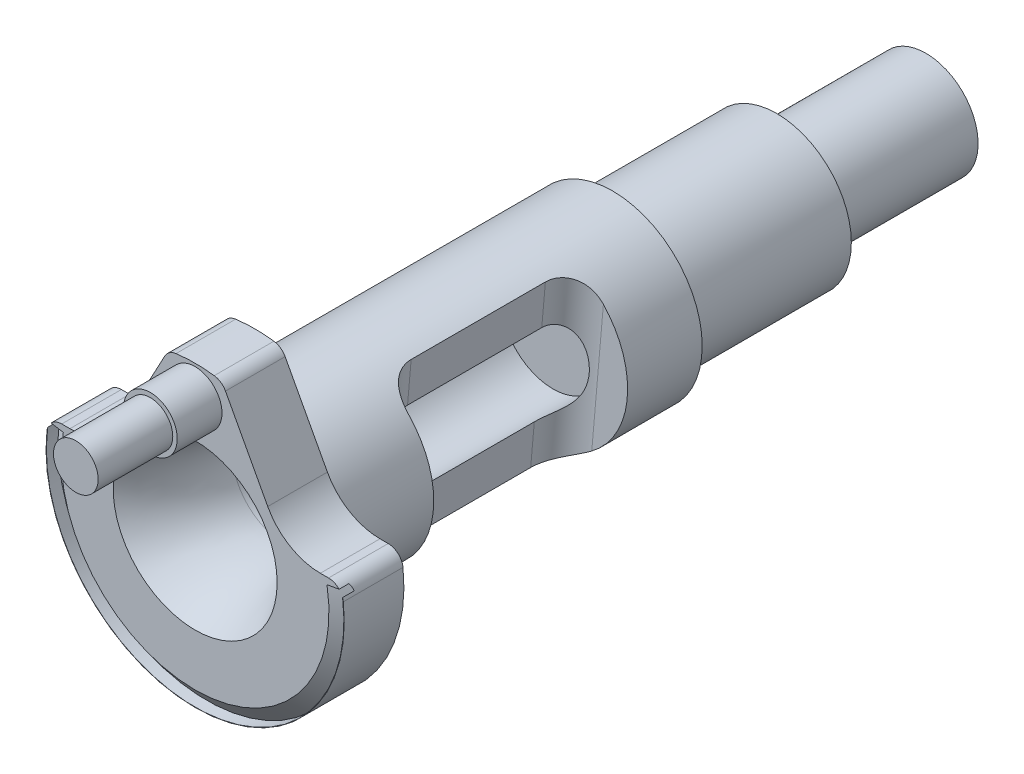
SolidWorks part; units mm, degrees
ref_plane "Front Plane" through (0, 0, 0) normal (0, 0, 1) x (1, 0, 0)
ref_plane "Top Plane" through (0, 0, 0) normal (0, 1, 0) x (1, 0, 0)
ref_plane "Right Plane" through (0, 0, 0) normal (1, 0, 0) x (0, 0, -1)
sketch "Sketch1" plane through (0, 0, 0) normal (0, 0, 1) x (1, 0, 0)
  circle A0 centre (0, 0) radius 5
  dimension "D1" = 10
extrude "Boss-Extrude1" add sketch "Sketch1" along normal blind 35
sketch "Sketch3" plane through (0, 0, 35) normal (0, 0, 1) x (1, 0, 0)
  circle A0 centre (0, 0) radius 5 construction
  circle A1 centre (0, 0) radius 5
  circle A2 centre (0, 0) radius 10
  dimension "D1" = 20
extrude "Boss-Extrude3" add sketch "Sketch3" along normal blind 4 contours A2
sketch "Sketch4" plane through (0, 0, 35) normal (0, 0, -1) x (-1, 0, 0)
  circle A0 centre (0, 0) radius 5 construction
  circle A1 centre (0, 0) radius 5
  circle A2 centre (0, 0) radius 6
  dimension "D1" = 12
extrude "Boss-Extrude4" add sketch "Sketch4" along normal blind 24
sketch "Sketch5" plane through (0, 0, 39) normal (0, 0, 1) x (1, 0, 0)
  line L0 (0, 0) -> (0, 50000) construction
  line L1 (-9.798, 2) -> (-6, 2)
  line L2 (-6, 2) -> (-1.8, 9.8367)
  line L3 (9.798, 2) -> (6, 2)
  line L4 (6, 2) -> (1.8, 9.8367)
  circle A0 centre (0, 0) radius 5 construction
  circle A1 centre (0, 0) radius 5
  circle A2 centre (0, 0) radius 10 construction
  circle A3 centre (0, 0) radius 10
  circle M6 centre (0, 0) radius 10
  dimension "D1" = 2
  dimension "D2" = 1.8
  dimension "D3" = 6
extrude "Cut-Extrude1" cut sketch "Sketch5" against normal through all contours L1 L2 M6 | L4 L3 M6 region at (-6.0605, 5.4525, 39) region at (6.0605, 5.4525, 39)
fillet "Fillet1" radius 1 4 edges at (-1.8, 9.8367, 37) (1.8, 9.8367, 37) (9.798, 2, 37) (-9.798, 2, 37)
sketch "Sketch6" plane through (0, 0, 39) normal (0, 0, 1) x (1, 0, 0)
  circle A0 centre (0, 0) radius 3.5
  dimension "D1" = 7
extrude "Cut-Extrude2" cut sketch "Sketch6" against normal blind 24
chamfer "Chamfer1" distance 2 1 edges at (3.5, 0, 39)
fillet "Fillet2" radius 10 1 edges at (3.5, 0, 37)
sketch "Sketch7" plane through (0, 0, 39) normal (0, 0, 1) x (1, 0, 0)
  line L0 (0, 0) -> (0, -50000) construction
  circle A0 centre (0, 8) radius 1.5
  dimension "D1" = 3
  dimension "D2" = 8
extrude "Boss-Extrude5" add sketch "Sketch7" along normal blind 8
fillet "Fillet3" radius 4 2 edges at (6, 2, 37) (-6, 2, 37)
sketch "Sketch8" plane through (0, 0, 0) normal (1, 0, 0) x (0, 0, -1)
  line L0 (-1000, 0) -> (49000, 0) construction
  line L1 (-39, -8.9766) -> (-38.2, -9.9995)
  line L2 (-39, 1.1111) -> (-39, -10) construction
  line L3 (-39, -8.9766) -> (-39, -9.9766)
  line L4 (-39, -9.9766) -> (-38.2, -9.9766)
  dimension "D1" = 0.8
  dimension "D2" = 1
  dimension "D3" = 8.9766
  dimension "D4" = 9.9995
revolve "Cut-Revolve1" cut sketch "Sketch8" angle 200 mid plane about L0 region at (0, -9.6432, 38.7393)
sketch "Sketch9" plane through (0, 0, 39) normal (0, 0, 1) x (1, 0, 0)
  circle A0 centre (0, 8) radius 1.5 construction
  circle A1 centre (0, 8) radius 1.5
  circle A2 centre (0, 8) radius 1.8
  dimension "D1" = 3.6
extrude "Boss-Extrude6" add sketch "Sketch9" along normal blind 3
sketch "Sketch13" plane through (0, 0, 15) normal (0, 0, 1) x (1, 0, 0)
  line L0 (0, 0) -> (0, -50000) construction
  line L1 (0, 0) -> (-5.4791, 0.4794)
  circle A0 centre (0, 0) radius 5.5 construction
  dimension "D1" = 85
sketch "Sketch10" plane through (0, 0, 0) normal (0, 0, -1) x (-1, 0, 0)
  circle A0 centre (0, 0) radius 3.5
  dimension "D1" = 7
extrude "Boss-Extrude7" add sketch "Sketch10" along normal blind 10
ref_plane "Plane1" through (5.9772, -0.5229, 0) normal (0.9962, -0.0872, 0) x (0, 0, -1)
sketch "Sketch14" plane through (5.9772, -0.5229, 0) normal (0.9962, -0.0872, 0) x (0, 0, -1)
  line L0 (-35, -6) -> (-11, -6) construction
  line L1 (-11, 6) -> (-35, 6) construction
  line L2 (-35, -6) -> (-11, -6)
  line L3 (-11, 6) -> (-35, 6)
  line L5 (-29, 6) -> (-16, 6)
  line L6 (-29, 6) -> (-29, -6)
  line L7 (-29, -6) -> (-16, -6)
  line L8 (-16, 6) -> (-16, -6)
  dimension "D1" = 5
  dimension "D2" = 6
extrude "Cut-Extrude3" cut sketch "Sketch14" against normal blind 4 contours L8 L3 L6 L2 region at (5.9772, -0.5229, 22.5)
fillet "Fillet4" radius 2 2 edges at (2.3641, 4.074, 16) (2.3641, 4.074, 29)
